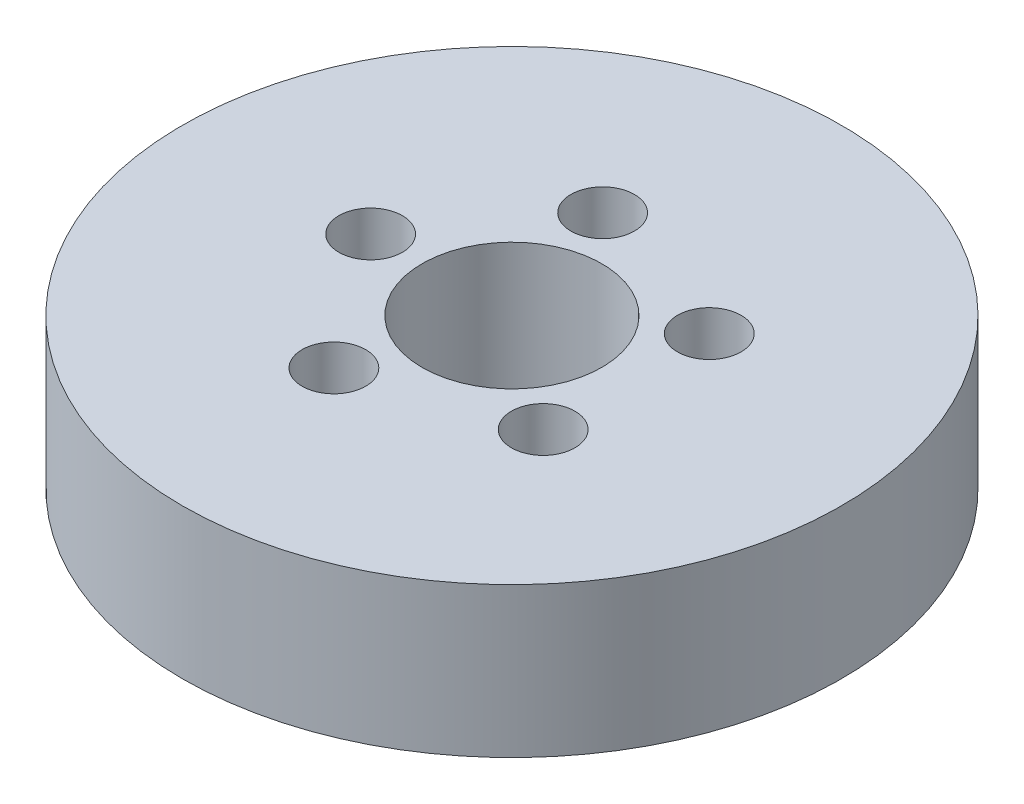
SolidWorks part; units mm, degrees
ref_plane "Front Plane" through (0, 0, 0) normal (0, 0, 1) x (1, 0, 0)
ref_plane "Top Plane" through (0, 0, 0) normal (0, 1, 0) x (1, 0, 0)
ref_plane "Right Plane" through (0, 0, 0) normal (1, 0, 0) x (0, 0, -1)
sketch "Sketch1" plane through (0, 0, 0) normal (0, 1, 0) x (1, 0, 0)
  circle A0 centre (0, 0) radius 55
  dimension "FLANGE_OD" = 110
extrude "Boss-Extrude1" add sketch "Sketch1" along normal blind 25
sketch "Sketch2" plane through (0, 0, 0) normal (0, 1, 0) x (1, 0, 0)
  circle A0 centre (0, 0) radius 15
  dimension "BORE_D" = 30
extrude "Cut-Extrude1" cut sketch "Sketch2" along normal through all
sketch "Sketch3" plane through (0, 25, 0) normal (0, 1, 0) x (1, 0, 0)
  circle A0 centre (0, 0) radius 23.5796 construction
  circle A1 centre (-23.5796, 0) radius 5.3031
  dimension "BOLT_D" = 10.6063
  dimension "BOLT_PCD" = 47.1592
extrude "Cut-Extrude2" cut sketch "Sketch3" against normal blind 18.0193
pattern_circular "CirPattern1" count 5 over 360 about axis through (0, 0, 0) along (0, 1, 0) of "Cut-Extrude2"
